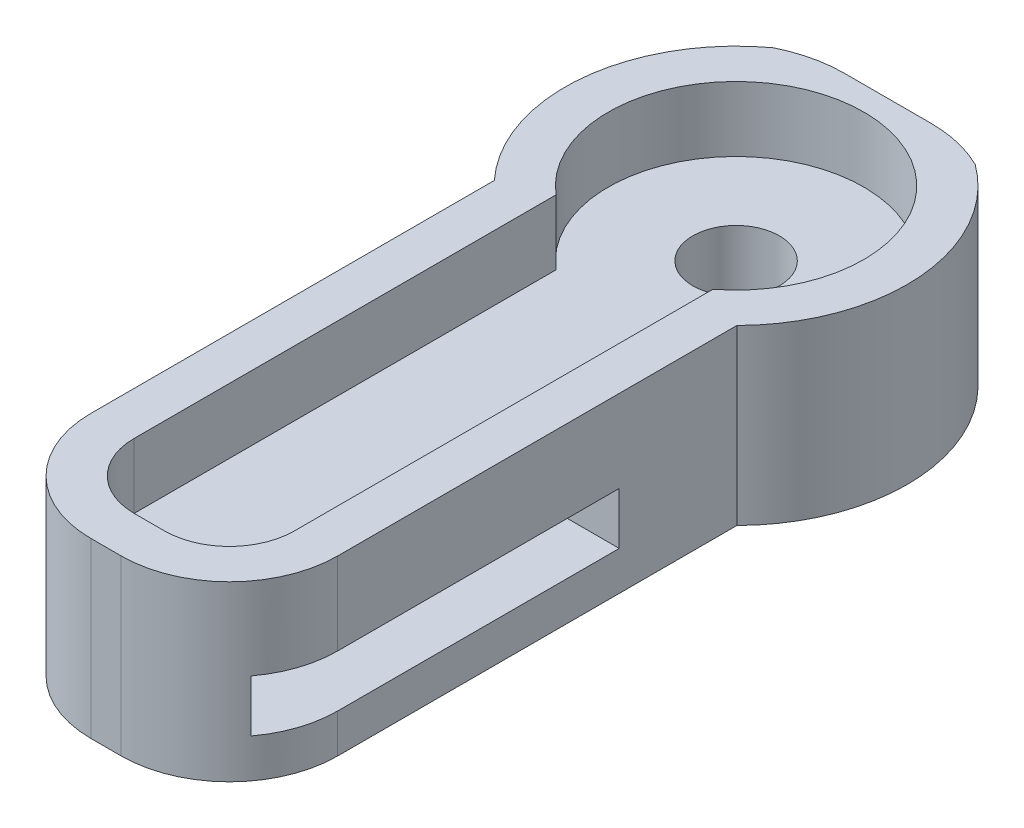
SolidWorks part; units mm, degrees
ref_plane "Front" through (0, 0, 0) normal (0, 0, 1) x (1, 0, 0)
ref_plane "Top" through (0, 0, 0) normal (0, 1, 0) x (1, 0, 0)
ref_plane "Right" through (0, 0, 0) normal (1, 0, 0) x (0, 0, -1)
sketch "草图1" plane through (0, 0, 0) normal (0, 1, 0) x (1, 0, 0)
  line L1 (4, -9) -> (-4, -9)
  line L2 (4, -9) -> (4, 9)
  line L3 (4, 9) -> (-4, 9)
  line L4 (-4, -9) -> (-4, 9)
  line L5 (4, -9) -> (-4, 9) construction
  line L6 (4, 9) -> (-4, -9) construction
  point P0 (0, 0)
  dimension "D1" = 8
  dimension "D2" = 18
extrude "凸台-拉伸1" add sketch "草图1" along normal blind 4
sketch "草图5" plane through (0, 4, 0) normal (0, 1, 0) x (1, 0, 0)
  line L0 (0, 14.2199) -> (0, 8.45) construction
  line L1 (-4, -9) -> (4, -9) construction
  line L2 (1.8021, -8) -> (-1.8979, -8)
  line L3 (1.8021, -8) -> (1.8021, 3.1644)
  line L5 (-1.8979, -8) -> (-1.8979, 3.2416)
  line L6 (1.8021, -8) -> (0, -0.8329) construction
  line L7 (0, -0.8329) -> (-1.8979, -8) construction
  line L8 (0, 3.575) -> (0, -12.7444) construction
  arc A0 (1.8021, 3.1644) -> (-1.8979, 3.2416) centre (0, 5.5) ccw
  point P5 (0, -0.8329)
  dimension "D1" = 5.9
  dimension "D2" = 13.5
  dimension "D3" = 1
  dimension "D4" = 3.7
extrude "切除-拉伸4" cut sketch "草图5" against normal blind 1.5
sketch "草图6" plane through (4, 0, 0) normal (1, 0, 0) x (0, 0, -1)
  line L0 (-13.7393, 1.5) -> (14.7183, 1.5) construction
  line L1 (-9, 4) -> (9, 4) construction
  line L2 (-9, 4) -> (-9, 0) construction
  line L3 (0, 0.9) -> (-8, 0.9)
  line L4 (0, 0.9) -> (0, 2.1)
  line L5 (0, 2.1) -> (-8, 2.1)
  line L6 (-8, 0.9) -> (-8, 2.1)
  line L7 (0, 0.9) -> (-8, 2.1) construction
  line L8 (0, 2.1) -> (-8, 0.9) construction
  point P5 (-4, 1.5)
  dimension "D1" = 2.5
  dimension "D2" = 1.2
  dimension "D3" = 8
  dimension "D4" = 1
extrude "切除-拉伸5" cut sketch "草图6" against normal through all
sketch "草图7" plane through (0, 2.5, 0) normal (0, 1, 0) x (1, 0, 0)
  circle A0 centre (0, 5.5) radius 1
  dimension "D1" = 2
extrude "切除-拉伸6" cut sketch "草图7" against normal through all
fillet "圆角1" radius 3 2 edges at (4, 2, -9) (-4, 2, -9)
fillet "圆角2" radius 2 2 edges at (4, 2, 9) (-4, 2, 9)
fillet "圆角3" radius 1.5 2 edges at (-1.8979, 3.25, 8) (1.8021, 3.25, 8)
sketch "草图9" plane through (0, 4, 0) normal (0, 1, 0) x (1, 0, 0)
  line L8 (-2.8979, 2.8158) -> (-2.8979, -6.5)
  line L9 (2.8021, -6.5) -> (2.8021, 2.716)
  line L10 (-2.8979, 2.8158) -> (-2.8979, -6.5)
  line L11 (2.8021, -6.5) -> (2.8021, 2.716)
  arc A10 (0.3021, -9) -> (2.8021, -6.5) centre (0.3021, -6.5) ccw
  arc A11 (-2.8979, -6.5) -> (-0.3979, -9) centre (-0.3979, -6.5) ccw
  arc A12 (2.8021, 2.716) -> (-2.8979, 2.8158) centre (0, 5.5) ccw
  arc A13 (0.3021, -9) -> (2.8021, -6.5) centre (0.3021, -6.5) ccw
  arc A14 (-2.8979, -6.5) -> (-0.3979, -9) centre (-0.3979, -6.5) ccw
  arc A15 (2.8021, 2.716) -> (-2.8979, 2.8158) centre (0, 5.5) ccw
  dimension "D1" = 1
extrude "切除-拉伸7" cut sketch "草图9" against normal through all and the other way through all flip side to cut body kept at (2.3323, 4, -8.6879)
